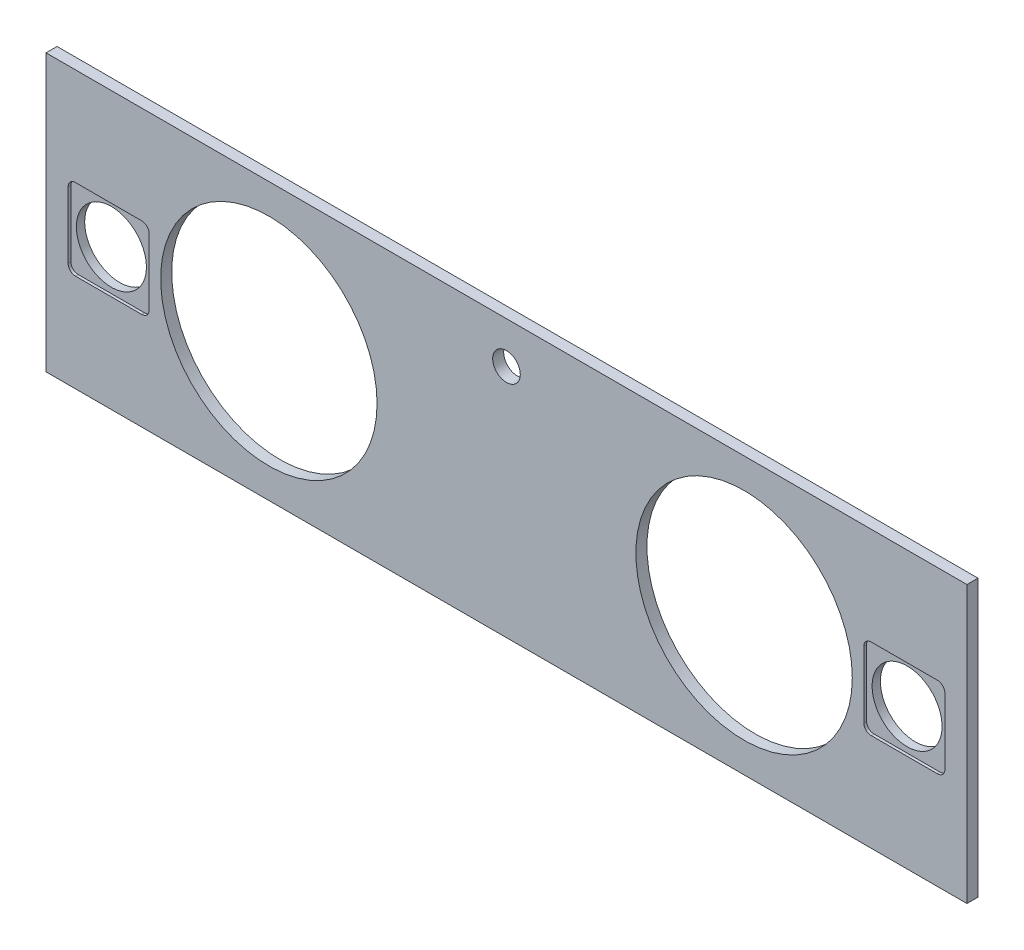
SolidWorks part; units mm, degrees
material "Pine"
ref_plane "Front Plane" through (0, 0, 0) normal (0, 0, 1) x (1, 0, 0)
ref_plane "Top Plane" through (0, 0, 0) normal (0, 1, 0) x (1, 0, 0)
ref_plane "Right Plane" through (0, 0, 0) normal (1, 0, 0) x (0, 0, -1)
sketch "Sketch1" plane through (0, 0, 0) normal (0, 0, 1) x (1, 0, 0)
  line L5 (500, 424.6951) -> (500, -112.2601) construction
  line L6 (0, 0) -> (1000, 0)
  line L10 (0, 0) -> (0, 300)
  line L11 (0, 300) -> (1000, 300)
  line L12 (1000, 0) -> (1000, 300)
  circle A0 centre (242, 150) radius 117.5
  circle A2 centre (758, 150) radius 117.5
  circle A3 centre (68, 150) radius 38
  circle A4 centre (932, 150) radius 38
  dimension "D1" = 235
  dimension "D8" = 76
  dimension "D2" = 1000
  dimension "D3" = 300
  dimension "D4" = 242
  dimension "D5" = 150
  dimension "D6" = 68
  dimension "D7" = 150
  dimension "D9" = 242
extrude "Boss-Extrude1" add sketch "Sketch1" along normal blind 12 contours A2 | A0 | L10 L11 L12 L6 | A3 | A4 region at (758, 150, 0)
sketch "Sketch4" plane through (0, 0, 12) normal (0, 0, 1) x (1, 0, 0)
  line L0 (0, 0) -> (0, 300) construction
  line L1 (32, 194) -> (104, 194)
  line L2 (24, 186) -> (24, 114)
  line L3 (32, 106) -> (104, 106)
  line L4 (112, 186) -> (112, 114)
  line L5 (0, 0) -> (0, 300) construction
  line L6 (0, 300) -> (1000, 300) construction
  line L7 (500, -84.0445) -> (500, 394.2312) construction
  line L8 (968, 106) -> (896, 106)
  line L9 (888, 186) -> (888, 114)
  line L10 (968, 194) -> (896, 194)
  line L11 (976, 186) -> (976, 114)
  arc A0 (104, 194) -> (112, 186) centre (104, 186) cw
  arc A1 (104, 106) -> (112, 114) centre (104, 114) ccw
  arc A2 (24, 114) -> (32, 106) centre (32, 114) ccw
  arc A3 (24, 186) -> (32, 194) centre (32, 186) cw
  arc A4 (896, 106) -> (888, 114) centre (896, 114) cw
  arc A5 (896, 194) -> (888, 186) centre (896, 186) ccw
  arc A6 (976, 114) -> (968, 106) centre (968, 114) cw
  arc A7 (976, 186) -> (968, 194) centre (968, 186) ccw
  point P16 (67.7235, 149.5451)
  dimension "D1" = 8
  dimension "D2" = 88
  dimension "D3" = 88
  dimension "D4" = 24
  dimension "D5" = 106
  dimension "D6" = 500
extrude "Cut-Extrude1" cut sketch "Sketch4" against normal blind 3 contours L2 A2 L3 A1 L4 A0 L1 A3 | L8 A4 L9 A5 L10 A7 L11 A6
sketch "Sketch6" plane through (0, 0, 12) normal (0, 0, 1) x (1, 0, 0)
  line L2 (0, 300) -> (1000, 300) construction
  line L3 (500, 300) -> (500, 241.385) construction
  circle A0 centre (500, 255) radius 15
  point P6 (0, 0)
  point P7 (500, 265)
  dimension "D3" = 30
  dimension "D2" = 45
extrude "Cut-Extrude2" cut sketch "Sketch6" against normal up to surface (12 mm away) up to face at (894, 150, 0)
equation "\"LENGTH\" = 1000mm"
equation "\"D2@Sketch1\"=\"LENGTH\""
equation "\"D6@Sketch4\"=\"LENGTH\"/2"
equation "\"PLY\"= 12mm"
equation "\"D1@Boss-Extrude1\"=\"PLY\""
equation "\"WIDTH\" = 300mm"
equation "\"CENTER_BRACE_LENGTH\" = 393mm"
equation "\"PANEL_WIDTH\"= \"LENGTH\" - \"CENTER_BRACE_LENGTH\" * 2 - \"PLY\" * 4"
equation "\"PANEL_SMALL_HEIGHT\" = 70mm"
